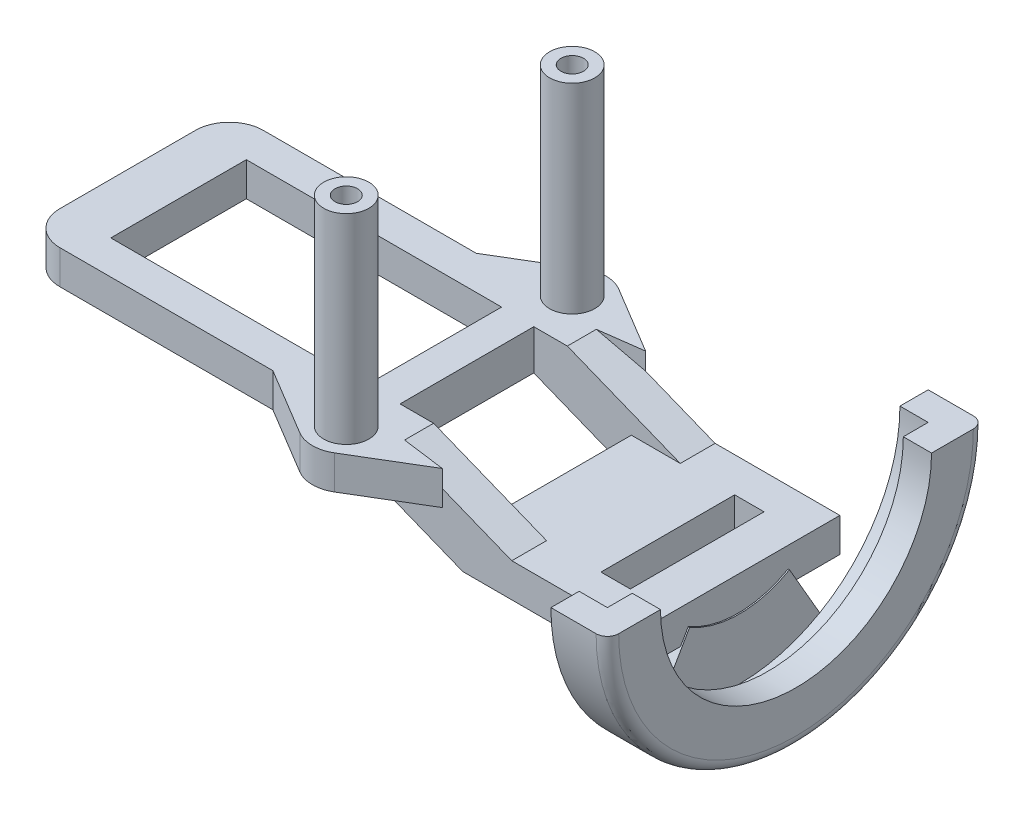
SolidWorks part; units mm, degrees
note: The reader was unsure of these and kept them because the rebuilt part matched: shared geometry of "Esquisse8<5>".
material "ABS"
ref_plane "Front" through (0, 0, 0) normal (0, 0, 1) x (1, 0, 0)
ref_plane "Top" through (0, 0, 0) normal (0, 1, 0) x (1, 0, 0)
ref_plane "Right" through (0, 0, 0) normal (1, 0, 0) x (0, 0, -1)
sketch "Sketch1" plane through (0, 0, 0) normal (0, 1, 0) x (1, 0, 0)
  line L0 (4.5, 9) -> (27.1, 9) construction
  line L1 (4.5, 15) -> (27.1, 15)
  line L2 (4.5, 15) -> (4.5, 3)
  line L3 (4.5, 3) -> (27.1, 3)
  line L4 (27.1, 15) -> (27.1, 3)
  line L5 (33, 3) -> (33, 0)
  line L6 (0, 18) -> (33, 18)
  line L7 (0, 18) -> (0, 0)
  line L8 (0, 0) -> (33, 0)
  line L9 (33, 18) -> (33, 15)
  line L10 (31.6, 15) -> (33, 15)
  line L11 (31.6, 15) -> (31.6, 3)
  line L12 (31.6, 3) -> (33, 3)
  dimension "D1" = 3
  dimension "D2" = 33
  dimension "D5" = 22.6
  dimension "D3" = 4.5
  dimension "D6" = 4.5
  dimension "D4" = 12
extrude "Boss-Extrude1" add sketch "Sketch1" along normal blind 3
sketch "Esquisse4" plane through (0, 0, 0) normal (0, -1, 0) x (1, 0, 0)
  line L0 (31.6, -9) -> (27.1, -9) construction
  line L1 (31.6, -15) -> (31.6, -3) construction
  line L2 (27.1, -15) -> (27.1, -3) construction
  line L3 (29.35, 1) -> (29.35, -2.7456) construction
  line L4 (0, -18) -> (0, 0) construction
  line L5 (0, 0) -> (33, 0) construction
  line L6 (29.35, -17) -> (36.85, -18)
  line L7 (21.85, -18) -> (29.35, -17)
  line L8 (36.85, 0) -> (30.893, 3.5728)
  line L9 (27.807, 3.5728) -> (21.85, 0)
  line L10 (21.85, 0) -> (29.35, -1)
  line L11 (29.35, -1) -> (36.85, 0)
  line L12 (27.807, -21.5728) -> (21.85, -18)
  line L13 (36.85, -18) -> (30.893, -21.5728)
  arc A0 (30.893, -21.5728) -> (27.807, -21.5728) centre (29.35, -19) cw
  arc A4 (30.893, 3.5728) -> (27.807, 3.5728) centre (29.35, 1) ccw
  dimension "D1" = 3
  dimension "D2" = 15
  dimension "D3" = 2
  dimension "D4" = 29.35
  dimension "D5" = 1
extrude "Boss.-Extru.2" add sketch "Esquisse4" against normal blind 3
sketch "Esquisse1" plane through (0, 0, 0) normal (0, 0, 1) x (1, 0, 0)
  line L0 (43, -1) -> (33, 3)
  line L1 (43, -1) -> (54.0471, -1)
  line L2 (54.0471, -1) -> (54.0471, -4)
  line L3 (54.0471, -4) -> (38.6671, -4)
  line L4 (38.6671, -4) -> (28.6671, 0)
  line L5 (28.6671, 0) -> (28.6671, 3)
  line L6 (33, 3) -> (28.6671, 3)
  dimension "D1" = 3
  dimension "D2" = 15.38
  dimension "D3" = 10
  dimension "D4" = 4
  dimension "D5" = 3
extrude "Boss.-Extru.1" add sketch "Esquisse1" against normal up to surface (18 mm away) contours L4 L5 L6 L0 L1 L2 L3 up to face at (10.925, 1.5, -18)
sketch "Esquisse3" plane through (0, -4, 0) normal (0, -1, 0) x (1, 0, 0)
  line L0 (38.6671, -18) -> (38.6671, 0) construction
  line L1 (30.0309, -3.08) -> (38.6671, -3.08)
  line L2 (30.0309, -3.08) -> (30.0309, -14.92)
  line L3 (30.0309, -14.92) -> (38.6671, -14.92)
  line L4 (38.6671, -3.08) -> (38.6671, -14.92)
  line L6 (30.0309, -9) -> (38.6671, -9) construction
  line L7 (0, -18) -> (0, 0) construction
  line L8 (38.6671, -18) -> (28.6671, -18) construction
  line L9 (38.6671, 0) -> (28.6671, 0) construction
  line L11 (47.815, -3.08) -> (50.415, -3.08)
  line L12 (47.815, -3.08) -> (47.815, -14.92)
  line L13 (47.815, -14.92) -> (50.415, -14.92)
  line L14 (50.415, -3.08) -> (50.415, -14.92)
  point P6 (49.115, -14.92)
  dimension "D1" = 11.84
  dimension "D2" = 2.6
  dimension "D3" = 49.115
extrude "Enlèv. mat.-Extru.1" cut sketch "Esquisse3" against normal through all
sketch "Esquisse5" plane through (0, 0, 0) normal (0, 0, 1) x (1, 0, 0)
  line L0 (38, -1) -> (36.6375, 0.09)
  line L1 (36.6375, 0.09) -> (39.761, 3.9943)
  line L2 (39.761, 3.9943) -> (41.1235, 2.9043)
  line L3 (41.1235, 2.9043) -> (38, -1)
  dimension "D1" = 5
  dimension "D2" = 5
sketch "Esquisse6" plane through (0, 3, 0) normal (0, 1, 0) x (1, 0, 0)
  line L0 (4.5, 9) -> (27.1, 9) construction
  line L1 (4.5, 15) -> (4.5, 3) construction
  line L2 (27.1, 15) -> (27.1, 3) construction
  circle A1 centre (29.35, -1) radius 2
  circle A3 centre (29.35, 19) radius 2
  arc A4 (30.893, 21.5728) -> (27.807, 21.5728) centre (29.35, 19) ccw construction
  dimension "D2" = 4
extrude "Boss.-Extru.3" add sketch "Esquisse6" along normal blind 17.7
sketch "Esquisse7" plane through (0, 20.7, 0) normal (0, 1, 0) x (1, 0, 0)
  circle A0 centre (29.35, 19) radius 1
  circle A1 centre (29.35, -1) radius 1
  circle A2 centre (29.35, -1) radius 2 construction
  dimension "D1" = 2
  dimension "D2" = 2
extrude "Enlèv. mat.-Extru.3" cut sketch "Esquisse7" against normal blind 4
ref_plane "Plan1" through (0, 0, -9) normal (0, 0, 1) x (1, 0, 0)
sketch "Esquisse8" plane through (0, 0, -9) normal (0, 0, 1) x (1, 0, 0)
  line L0 (74.4387, 4.84) -> (82.0597, 4.84) construction
  line L1 (43, -1) -> (54.0471, -1) construction
  line L2 (54.165, -9.36) -> (54.165, -11.86)
  line L3 (54.165, -4) -> (54.165, -9.36)
  line L4 (54.165, -9.36) -> (56.665, -9.36)
  line L5 (56.665, -9.36) -> (56.665, -7.16)
  line L6 (56.665, -7.16) -> (59.165, -7.16)
  line L8 (59.165, -7.16) -> (59.165, -11.86)
  line L9 (59.165, -11.86) -> (51.665, -11.86)
  line L10 (51.665, -11.86) -> (51.665, -4)
  line L13 (51.665, -4) -> (54.165, -4)
  dimension "D1" = 5.84
  dimension "D2" = 3.75
  dimension "D3" = 14.2
  dimension "D4" = 12
  dimension "D5" = 2.5
  dimension "D6" = 2.5
  dimension "D7" = 2.5
  dimension "D8" = 2.5
revolve "Révolution1" add sketch "Esquisse8" angle 90 about L0
revolve "Revolve1" add sketch "Esquisse8<5>" angle 30 about L0
sketch "Esquisse8<5>" plane through (0, 0, -9) normal (0, 0, 1) x (1, 0, 0) same geometry as "Esquisse8"
fillet "Congé1" radius 3 2 edges at (0, 1.5, -18) (0, 1.5, 0)
fillet "Congé2" radius 1 1 edges at (59.165, -11.86, -9)
sketch "Sketch3" plane through (0, 0, -14.92) normal (0, 0, 1) x (1, 0, 0)
  line L0 (43, -1) -> (54.0471, -1) construction
  line L1 (43, 7.3534) -> (30.0309, 7.3534)
  line L2 (43, 7.3534) -> (43, -1)
  line L3 (43, -1) -> (30.0309, -1)
  line L4 (30.0309, 7.3534) -> (30.0309, -1)
  line L5 (30.0309, 3) -> (30.0309, -0.5455) construction
extrude "Cut-Extrude1" cut sketch "Sketch3" along normal up to surface (11.84 mm away) up to face at (34.0792, 0.4375, -3.08)
